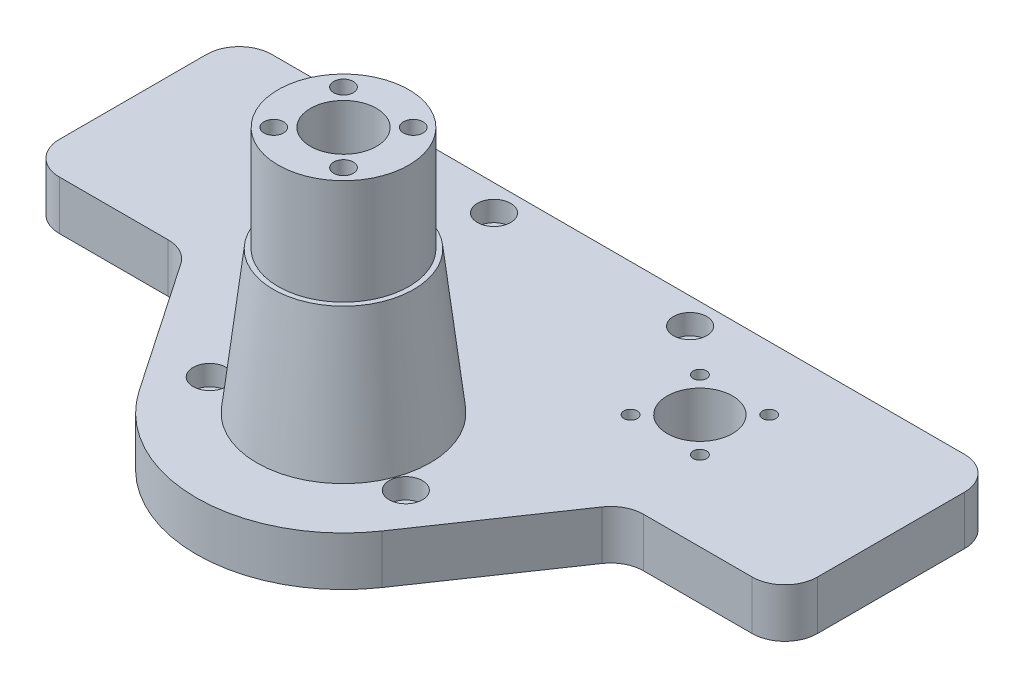
SolidWorks part; units mm, degrees
material "PLA Infill"
ref_plane "Front Plane" through (0, 0, 0) normal (0, 0, 1) x (1, 0, 0)
ref_plane "Top Plane" through (0, 0, 0) normal (0, 1, 0) x (1, 0, 0)
ref_plane "Right Plane" through (0, 0, 0) normal (1, 0, 0) x (0, 0, -1)
sketch "Sketch1" plane through (0, 0, 0) normal (0, 1, 0) x (1, 0, 0)
  line L0 (0, 0) -> (55, 54.0672) construction
  line L1 (55, 54.0672) -> (-55, 54.0672) construction
  line L2 (-55, 54.0672) -> (0, 0) construction
  line L3 (-79.7903, 37.1722) -> (-37.1854, -25.3425) construction
  line L4 (-55, 84.0672) -> (55, 84.0672)
  line L5 (37.1854, -25.3425) -> (79.7903, 37.1722) construction
  line L6 (-55, 84.0672) -> (-106, 84.0672)
  line L7 (-116, 74.0672) -> (-116, 29.0672)
  line L8 (-106, 19.0672) -> (-72.7378, 19.0672)
  line L9 (-64.4743, 14.6989) -> (-37.1854, -25.3425)
  line L10 (0, -1000) -> (0, 49000) construction
  line L11 (64.4743, 14.6989) -> (37.1854, -25.3425)
  line L12 (106, 19.0672) -> (72.7378, 19.0672)
  line L13 (116, 74.0672) -> (116, 29.0672)
  line L14 (55, 84.0672) -> (106, 84.0672)
  circle A0 centre (-55, 54.0672) radius 30 construction
  circle A1 centre (55, 54.0672) radius 30 construction
  circle A2 centre (0, 0) radius 45 construction
  arc A3 (-79.7903, 37.1722) -> (-55, 84.0672) centre (-55, 54.0672) cw construction
  arc A4 (55, 84.0672) -> (79.7903, 37.1722) centre (55, 54.0672) cw construction
  arc A5 (-37.1854, -25.3425) -> (37.1854, -25.3425) centre (0, 0) ccw
  arc A6 (-72.7378, 19.0672) -> (-64.4743, 14.6989) centre (-72.7378, 9.0672) cw
  arc A7 (-116, 29.0672) -> (-106, 19.0672) centre (-106, 29.0672) ccw
  arc A8 (-106, 84.0672) -> (-116, 74.0672) centre (-106, 74.0672) ccw
  arc A9 (72.7378, 19.0672) -> (64.4743, 14.6989) centre (72.7378, 9.0672) ccw
  arc A10 (116, 29.0672) -> (106, 19.0672) centre (106, 29.0672) cw
  arc A11 (106, 84.0672) -> (116, 74.0672) centre (106, 74.0672) cw
  point P23 (-67.4514, 19.0672)
  dimension "D3" = 60
  dimension "D4" = 90
  dimension "D5" = 10
  dimension "D6" = 61
  dimension "D1" = 110
  dimension "D2" = 77.125
  dimension "D7" = 35
extrude "Main Body" add sketch "Sketch1" along normal blind 15 contours A5 L11 A9 L12 A10 L13 A11 L14 L4 L6 A8 L7 A7 L8 A6 L9
sketch "Sketch3" plane through (0, 15, 0) normal (0, 1, 0) x (1, 0, 0)
  circle A0 centre (0, 0) radius 45 construction
  circle A1 centre (0, 0) radius 45 construction
  circle A2 centre (0, 0) radius 21.5
  dimension "D1" = 43
extrude "Front Extrusion" add sketch "Sketch3" along normal blind 75.7
ref_plane "First Bearing Section" through (0, 58.5, 0) normal (0, 1, 0) x (1, 0, 0)
sketch "Front Loft" plane through (0, 58.5, 0) normal (0, 1, 0) x (1, 0, 0)
  circle A0 centre (0, 0) radius 21.5
  dimension "D1" = 43
sketch "Back Loft" plane through (0, 15, 0) normal (0, 1, 0) x (1, 0, 0)
  circle A0 centre (0, 0) radius 26.5
  dimension "D1" = 53
loft "Lofted Taper" add profiles "Front Loft", "Back Loft" connector at (0, 58.5, 21.5) connector at (0, 15, 26.5)
sketch "Sketch4" plane through (0, 0, 0) normal (0, -1, 0) x (1, 0, 0)
  line L0 (0, -1000) -> (0, 49000) construction
  line L1 (-45, 0) -> (45, 0) construction
  line L2 (-85, -54.0672) -> (-25, -54.0672) construction
  line L3 (55, -54.0672) -> (-55, -54.0672) construction
  line L4 (-55, -24.0672) -> (-55, -84.0672) construction
  line L5 (-10.6773, 10.6773) -> (0, 0) construction
  line L6 (-10.6773, -10.6773) -> (0, 0) construction
  line L7 (-65.6066, -43.4606) -> (-55, -54.0672) construction
  line L8 (-106, -84.0672) -> (106, -84.0672) construction
  line L9 (106, -84.0672) -> (-106, -84.0672) construction
  line L10 (-30, -76.0672) -> (0, -76.0672) construction
  line L11 (-30, -76.0672) -> (-30, 10.9328) construction
  line L12 (-30, 10.9328) -> (0, 10.9328) construction
  line L13 (0, -76.0672) -> (0, 10.9328) construction
  circle A0 centre (55, -54.0672) radius 30 construction
  circle A1 centre (0, 0) radius 45 construction
  circle A2 centre (-55, -54.0672) radius 30 construction
  circle A3 centre (55, -54.0672) radius 30 construction
  circle A4 centre (0, 0) radius 45 construction
  circle A5 centre (-55, -54.0672) radius 30 construction
  circle A6 centre (0, 0) radius 10.1
  circle A7 centre (-55, -54.0672) radius 10
  circle A10 centre (-10.6773, 10.6773) radius 3
  circle A13 centre (-10.6773, -10.6773) radius 3
  circle A14 centre (-65.6066, -43.4606) radius 2.05
  circle A15 centre (-65.6066, -64.6738) radius 2.05
  circle A16 centre (-44.3934, -64.6738) radius 2.05
  circle A17 centre (-44.3934, -43.4606) radius 2.05
  circle A18 centre (55, -54.0672) radius 10
  circle A19 centre (65.6066, -64.6738) radius 2.05
  circle A20 centre (44.3934, -64.6738) radius 2.05
  circle A21 centre (44.3934, -43.4606) radius 2.05
  circle A22 centre (65.6066, -43.4606) radius 2.05
  circle A23 centre (10.6773, -10.6773) radius 3
  circle A24 centre (10.6773, 10.6773) radius 3
  circle A25 centre (-30, -76.0672) radius 3
  circle A26 centre (-30, 10.9328) radius 3
  circle A27 centre (30, -76.0672) radius 3
  circle A28 centre (30, 10.9328) radius 3
  dimension "D1" = 20.2
  dimension "D2" = 20
  dimension "D4" = 6
  dimension "D5" = 45
  dimension "D7" = 4.1
  dimension "D9" = 6
  dimension "D3" = 15.1
  dimension "D6" = 15
  dimension "D8" = 45
  dimension "D10" = 30
  dimension "D11" = 8
  dimension "D12" = 87
extrude "Bolt Holes" cut sketch "Sketch4" against normal through all
sketch "Sketch5" plane through (0, 0, 0) normal (0, -1, 0) x (1, 0, 0)
  line L0 (-14.2836, 7.0711) -> (-9.7707, 2.5582)
  line L1 (-7.0711, 14.2836) -> (-2.5582, 9.7707)
  line L2 (-10.6773, 10.6773) -> (0, 0) construction
  line L3 (-1000, 0) -> (49000, 0) construction
  line L4 (0, -1000) -> (0, 49000) construction
  line L5 (-14.2836, -7.0711) -> (-9.7707, -2.5582)
  line L6 (-7.0711, -14.2836) -> (-2.5582, -9.7707)
  line L7 (7.0711, -14.2836) -> (2.5582, -9.7707)
  line L8 (14.2836, -7.0711) -> (9.7707, -2.5582)
  line L9 (14.2836, 7.0711) -> (9.7707, 2.5582)
  line L10 (7.0711, 14.2836) -> (2.5582, 9.7707)
  circle A0 centre (-10.6773, 10.6773) radius 2 construction
  circle A1 centre (-10.6773, 10.6773) radius 5.1 construction
  circle A2 centre (0, 0) radius 10.1 construction
  arc A3 (-14.2836, 7.0711) -> (-7.0711, 14.2836) centre (-10.6773, 10.6773) cw
  circle A4 centre (0, 0) radius 10.1 construction
  arc A5 (-9.7707, 2.5582) -> (-2.5582, 9.7707) centre (0, 0) cw
  arc A6 (-14.2836, -7.0711) -> (-7.0711, -14.2836) centre (-10.6773, -10.6773) ccw
  arc A7 (-9.7707, -2.5582) -> (-2.5582, -9.7707) centre (0, 0) ccw
  arc A8 (14.2836, -7.0711) -> (7.0711, -14.2836) centre (10.6773, -10.6773) cw
  arc A9 (9.7707, -2.5582) -> (2.5582, -9.7707) centre (0, 0) cw
  arc A10 (14.2836, 7.0711) -> (7.0711, 14.2836) centre (10.6773, 10.6773) ccw
  arc A11 (9.7707, 2.5582) -> (2.5582, 9.7707) centre (0, 0) ccw
  dimension "D1" = 4
  dimension "D2" = 10.2
extrude "Bolt Recesses Rear" cut sketch "Sketch5" against normal blind 10
sketch "Sketch6" plane through (0, 15, 0) normal (0, 1, 0) x (1, 0, 0)
  circle A1 centre (30, 76.0672) radius 5.1
  circle A2 centre (-30, -10.9328) radius 3 construction
  circle A3 centre (30, -10.9328) radius 3 construction
  circle A4 centre (30, 76.0672) radius 3 construction
  circle A5 centre (-30, 76.0672) radius 3 construction
  circle A6 centre (-30, -10.9328) radius 3 construction
  circle A7 centre (30, -10.9328) radius 3 construction
  circle A8 centre (30, 76.0672) radius 3 construction
  circle A9 centre (-30, 76.0672) radius 3 construction
  circle A10 centre (-30, 76.0672) radius 5.1
  circle A11 centre (-30, -10.9328) radius 5.1
  circle A12 centre (30, -10.9328) radius 5.1
  dimension "D1" = 10.2
extrude "Bolt Recesses Front" cut sketch "Sketch6" against normal blind 6.2
sketch "Sketch7" plane through (0, 90.7, 0) normal (0, 1, 0) x (1, 0, 0)
  circle A0 centre (0, 0) radius 21.5 construction
  circle A1 centre (0, 0) radius 21.5
  circle A2 centre (0, 0) radius 20
  dimension "D1" = 40
extrude "Cut-Extrude1" cut sketch "Sketch7" against normal up to surface (32.2 mm away) up to plane "First Bearing Section"
sketch "Sketch8" plane through (0, 0, 0) normal (0, -1, 0) x (1, 0, 0)
  line L0 (0, -1000) -> (0, 49000) construction
  circle A0 centre (-65.6066, -64.6738) radius 2.05 construction
  circle A1 centre (-44.3934, -64.6738) radius 2.05 construction
  circle A2 centre (-44.3934, -43.4606) radius 2.05 construction
  circle A3 centre (-65.6066, -43.4606) radius 2.05 construction
  circle A4 centre (-65.6066, -64.6738) radius 2.05 construction
  circle A5 centre (-44.3934, -64.6738) radius 2.05 construction
  circle A6 centre (-44.3934, -43.4606) radius 2.05 construction
  circle A7 centre (-65.6066, -43.4606) radius 2.05 construction
  circle A8 centre (-65.6066, -43.4606) radius 3.55
  circle A9 centre (-44.3934, -43.4606) radius 3.55
  circle A10 centre (-44.3934, -64.6738) radius 3.55
  circle A11 centre (-65.6066, -64.6738) radius 3.55
  circle A12 centre (44.3934, -64.6738) radius 3.55
  circle A13 centre (44.3934, -43.4606) radius 3.55
  circle A14 centre (65.6066, -64.6738) radius 3.55
  circle A15 centre (65.6066, -43.4606) radius 3.55
  dimension "D1" = 7.1
extrude "Motor bolt head recesses" cut sketch "Sketch8" against normal blind 4.1
sketch "Sketch9" plane through (0, 0, 0) normal (0, -1, 0) x (1, 0, 0)
  line L0 (0, -1000) -> (0, 49000) construction
  line L1 (-116, -74.0672) -> (-116, -29.0672) construction
  line L2 (106, -84.0672) -> (-106, -84.0672) construction
  line L4 (-111, -75.0672) -> (-41, -75.0672) construction
  line L5 (-111, -75.0672) -> (-111, -28.0672) construction
  line L6 (-111, -28.0672) -> (-41, -28.0672) construction
  line L7 (-41, -75.0672) -> (-41, -28.0672) construction
  circle A0 centre (-111, -75.0672) radius 2
  circle A1 centre (-111, -28.0672) radius 2
  circle A2 centre (-41, -28.0672) radius 2
  circle A3 centre (-41, -75.0672) radius 2
  circle A4 centre (41, -75.0672) radius 2
  circle A5 centre (111, -75.0672) radius 2
  circle A6 centre (41, -28.0672) radius 2
  circle A7 centre (111, -28.0672) radius 2
  dimension "D3" = 4
  dimension "D1" = 5
  dimension "D2" = 9
  dimension "D4" = 70
  dimension "D5" = 47
extrude "Heat-set insert holes" cut sketch "Sketch9" against normal blind 6
sketch "Sketch10" plane through (0, 0, 0) normal (0, -1, 0) x (1, 0, 0)
  line L0 (0, -1000) -> (0, 49000) construction
  line L1 (-116, -74.0672) -> (-116, -29.0672) construction
  line L2 (106, -84.0672) -> (-106, -84.0672) construction
  line L4 (-101.5, -76.5672) -> (-51.5, -76.5672) construction
  line L5 (-101.5, -76.5672) -> (-101.5, -26.5672) construction
  line L6 (-101.5, -26.5672) -> (-51.5, -26.5672) construction
  line L7 (-51.5, -76.5672) -> (-51.5, -26.5672) construction
  circle A0 centre (-101.5, -76.5672) radius 1.6
  circle A1 centre (-101.5, -26.5672) radius 1.6
  circle A2 centre (-51.5, -26.5672) radius 1.6
  circle A3 centre (-51.5, -76.5672) radius 1.6
  circle A4 centre (101.5, -76.5672) radius 1.6
  circle A5 centre (51.5, -76.5672) radius 1.6
  circle A6 centre (51.5, -26.5672) radius 1.6
  circle A7 centre (101.5, -26.5672) radius 1.6
  dimension "D1" = 3.2
  dimension "D2" = 14.5
  dimension "D3" = 7.5
  dimension "D4" = 50
  dimension "D5" = 50
extrude "PCB Heat-set insert holes" cut sketch "Sketch10" against normal blind 4
sketch "Sketch11" plane through (0, 0, -84.0672) normal (0, 0, -1) x (-1, 0, 0)
  line L0 (0, -1000) -> (0, 49000) construction
  line L1 (-106, 0) -> (106, 0) construction
  circle A0 centre (-20, 7.5) radius 2
  circle A2 centre (20, 7.5) radius 2
  dimension "D1" = 4
  dimension "D2" = 7.5
  dimension "D3" = 20
extrude "Cut-Extrude2" cut sketch "Sketch11" against normal blind 6
